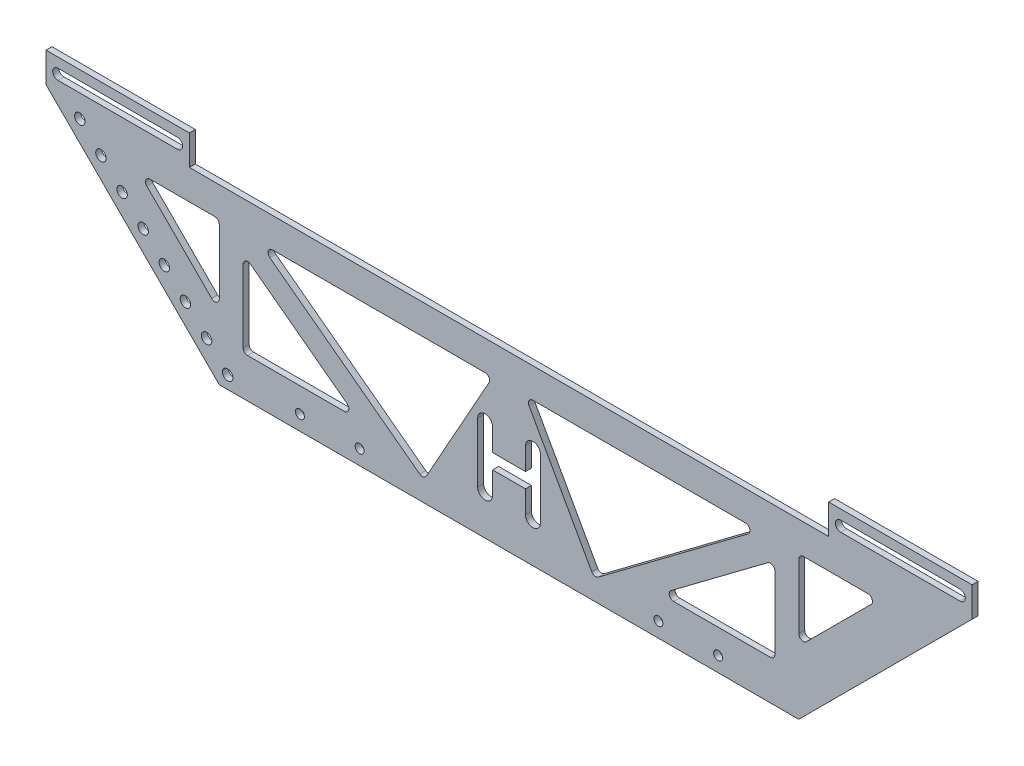
SolidWorks part; units mm, degrees
material "6061 合金"
ref_plane "前视基准面" through (0, 0, 0) normal (0, 0, 1) x (1, 0, 0)
ref_plane "上视基准面" through (0, 0, 0) normal (0, 1, 0) x (1, 0, 0)
ref_plane "右视基准面" through (0, 0, 0) normal (1, 0, 0) x (0, 0, -1)
sketch "草图1" plane through (0, 0, 0) normal (0, 0, 1) x (1, 0, 0)
  line L0 (-107, 30) -> (-107, 0)
  line L1 (-107, 0) -> (107, 0)
  line L2 (107, 0) -> (107, 30)
  line L3 (-107, 30) -> (-155, 30)
  line L5 (-97, -58) -> (97, -58)
  line L7 (155, 30) -> (107, 30)
  line L8 (0, 0) -> (0, -58) construction
  line L9 (-151, 25) -> (-111, 25) construction
  line L10 (-151, 25) -> (-151, 5) construction
  line L11 (-151, 5) -> (-111, 5) construction
  line L12 (-111, 25) -> (-111, 5) construction
  line L13 (111, 25) -> (111, 5) construction
  line L14 (151, 5) -> (111, 5) construction
  line L15 (151, 25) -> (151, 5) construction
  line L16 (151, 25) -> (111, 25) construction
  line L17 (-70, -53) -> (-50, -53) construction
  line L18 (70, -53) -> (50, -53) construction
  line L19 (-155, 30) -> (-155, 0)
  line L20 (-155, 0) -> (-97, -58)
  line L21 (97, -58) -> (155, 0)
  line L22 (155, 0) -> (155, 30)
  circle A0 centre (-151, 25) radius 1.5
  circle A1 centre (-111, 25) radius 1.5
  circle A2 centre (-111, 5) radius 1.5
  circle A3 centre (-151, 5) radius 1.5
  circle A4 centre (151, 5) radius 1.5
  circle A5 centre (111, 5) radius 1.5
  circle A6 centre (111, 25) radius 1.5
  circle A7 centre (151, 25) radius 1.5
  circle A8 centre (-70, -53) radius 1.5
  circle A9 centre (-50, -53) radius 1.5
  circle A10 centre (50, -53) radius 1.5
  circle A11 centre (70, -53) radius 1.5
  point P4 (0, 0)
  dimension "D5" = 3
  dimension "D10" = 3
  dimension "D1" = 30
  dimension "D2" = 214
  dimension "D3" = 58
  dimension "D4" = 48
  dimension "D6" = 5
  dimension "D7" = 5
  dimension "D8" = 4
  dimension "D9" = 4
  dimension "D11" = 20
  dimension "D12" = 50
  dimension "D13" = 5
  dimension "D14" = 45
extrude "凸台-拉伸1" add sketch "草图1" along normal blind 2
sketch "草图3" plane through (0, 0, 2) normal (0, 0, 1) x (1, 0, 0)
  line L0 (155, 0) -> (155, 30) construction
  line L1 (-155, 30) -> (155, 30)
  line L2 (-155, 30) -> (-155, 10)
  line L3 (-155, 10) -> (155, 10)
  line L4 (155, 30) -> (155, 10)
  circle A0 centre (151, 5) radius 1.5 construction
  dimension "D1" = 5
extrude "切除-拉伸2" cut sketch "草图3" against normal through all
sketch "草图4" plane through (0, 0, 2) normal (0, 0, 1) x (1, 0, 0)
  line L0 (-121.2261, -12.5607) -> (-99.5607, -34.2261)
  line L1 (-97, -33.1655) -> (-97, -11.5)
  line L2 (-98.5, -10) -> (-120.1655, -10)
  line L3 (107, 0) -> (-107, 0) construction
  line L4 (-155, 0) -> (-97, -58) construction
  line L5 (0, 0) -> (0, -58) construction
  line L6 (-97, -58) -> (97, -58) construction
  line L10 (-89, -19) -> (-89, -43.2868)
  line L11 (-87.5, -44.7868) -> (-55.1176, -44.7868)
  line L12 (-54.2176, -42.0868) -> (-86.6, -17.8)
  line L13 (-79.1667, -10) -> (-8, -10)
  line L14 (-6.6902, -12.231) -> (-27.6902, -49.856)
  line L15 (-29.9, -50.325) -> (-80.0667, -12.7)
  line L20 (29.9, -50.325) -> (80.0667, -12.7)
  line L21 (6.6902, -12.231) -> (27.6902, -49.856)
  line L22 (79.1667, -10) -> (8, -10)
  line L23 (54.2176, -42.0868) -> (86.6, -17.8)
  line L24 (87.5, -44.7868) -> (55.1176, -44.7868)
  line L25 (89, -19) -> (89, -43.2868)
  line L26 (98.5, -10) -> (120.1655, -10)
  line L27 (97, -33.1655) -> (97, -11.5)
  line L28 (121.2261, -12.5607) -> (99.5607, -34.2261)
  line L32 (0, 0) -> (0, -58)
  line L33 (0, -10.8561) -> (0, -58)
  line L37 (-5.5, -36.928) -> (-5.5, -44.428)
  line L41 (-5.5, -31.928) -> (5.5, -31.928)
  line L42 (-5.5, -36.928) -> (5.5, -36.928)
  line L44 (-5.5, -24.428) -> (-5.5, -31.928)
  line L45 (-10.5, -24.428) -> (-10.5, -44.428)
  line L47 (10.5, -24.428) -> (10.5, -44.428)
  line L48 (5.5, -24.428) -> (5.5, -31.928)
  line L49 (5.5, -36.928) -> (5.5, -44.428)
  arc A4 (-8, -10) -> (-6.6902, -12.231) centre (-8, -11.5) cw
  arc A5 (-27.6902, -49.856) -> (-29.9, -50.325) centre (-29, -49.125) cw
  arc A6 (-79.1667, -10) -> (-80.0667, -12.7) centre (-79.1667, -11.5) ccw
  arc A7 (-55.1176, -44.7868) -> (-54.2176, -42.0868) centre (-55.1176, -43.2868) ccw
  arc A8 (-89, -43.2868) -> (-87.5, -44.7868) centre (-87.5, -43.2868) ccw
  arc A9 (-89, -19) -> (-86.6, -17.8) centre (-87.5, -19) cw
  arc A10 (-99.5607, -34.2261) -> (-97, -33.1655) centre (-98.5, -33.1655) ccw
  arc A11 (-97, -11.5) -> (-98.5, -10) centre (-98.5, -11.5) ccw
  arc A12 (-121.2261, -12.5607) -> (-120.1655, -10) centre (-120.1655, -11.5) cw
  arc A13 (121.2261, -12.5607) -> (120.1655, -10) centre (120.1655, -11.5) ccw
  arc A14 (97, -11.5) -> (98.5, -10) centre (98.5, -11.5) cw
  arc A15 (99.5607, -34.2261) -> (97, -33.1655) centre (98.5, -33.1655) cw
  arc A16 (89, -19) -> (86.6, -17.8) centre (87.5, -19) ccw
  arc A17 (89, -43.2868) -> (87.5, -44.7868) centre (87.5, -43.2868) cw
  arc A18 (55.1176, -44.7868) -> (54.2176, -42.0868) centre (55.1176, -43.2868) cw
  arc A19 (79.1667, -10) -> (80.0667, -12.7) centre (79.1667, -11.5) cw
  arc A20 (27.6902, -49.856) -> (29.9, -50.325) centre (29, -49.125) ccw
  arc A21 (8, -10) -> (6.6902, -12.231) centre (8, -11.5) ccw
  arc A27 (-5.5, -24.428) -> (-10.5, -24.428) centre (-8, -24.428) ccw
  arc A28 (-10.5, -44.428) -> (-5.5, -44.428) centre (-8, -44.428) ccw
  arc A29 (10.5, -24.428) -> (5.5, -24.428) centre (8, -24.428) ccw
  arc A30 (5.5, -44.428) -> (10.5, -44.428) centre (8, -44.428) ccw
  point P26 (0, -34.428)
  point P32 (-8, -34.428)
  point P37 (8, -34.428)
  point P46 (-83.6667, -10)
  point P51 (-89, -44.7868)
  point P54 (-89, -16)
  point P59 (-97, -10)
  point P89 (97, -10)
  point P90 (89, -16)
  point P91 (89, -44.7868)
  point P92 (83.6667, -10)
  dimension "D7" = 1.5
  dimension "D1" = 10
  dimension "D2" = 15
  dimension "D3" = 8
  dimension "D4" = 8
  dimension "D5" = 6
  dimension "D6" = 8
  dimension "D8" = 29
extrude "切除-拉伸3" cut sketch "草图4" against normal through all and the other way through all contours L49 A30 L47 A29 L48 L41 L33 L42 | L45 A28 L37 L42 L33 L41 L44 A27 | L13 A6 L15 A5 L14 A4 | A9 L10 A8 L11 A7 L12 | A12 L0 A10 L1 A11 L2 | L22 A21 L21 A20 L20 A19 | A18 L24 A17 L25 A16 L23 | A15 L28 A13 L26 A14 L27 region at (-105.8777, -18.8777, 2) region at (-76.3188, -35.1852, 2) region at (-39.1442, -23.8182, 2) region at (39.1442, -23.8182, 2) region at (76.3188, -35.1852, 2) region at (105.8777, -18.8777, 2) region at (7.0188, -34.428, 2) region at (-7.0188, -34.428, 2)
sketch "草图5" plane through (0, 0, 2) normal (0, 0, 1) x (1, 0, 0)
  line L0 (-151, 5) -> (-111, 5) construction
  line L1 (-151, 6.75) -> (-111, 6.75)
  line L2 (-151, 3.25) -> (-111, 3.25)
  line L3 (111, 5) -> (151, 5) construction
  line L4 (111, 6.75) -> (151, 6.75)
  line L5 (111, 3.25) -> (151, 3.25)
  arc A0 (-151, 6.75) -> (-151, 3.25) centre (-151, 5) ccw
  arc A1 (-111, 3.25) -> (-111, 6.75) centre (-111, 5) ccw
  arc A2 (111, 6.75) -> (111, 3.25) centre (111, 5) ccw
  arc A3 (151, 3.25) -> (151, 6.75) centre (151, 5) ccw
  point P4 (-131, 5)
  point P13 (131, 5)
extrude "切除-拉伸4" cut sketch "草图5" against normal through all
sketch "草图7" plane through (0, 0, 2) normal (0, 0, 1) x (1, 0, 0)
  line L0 (-155, 0) -> (-151.4645, 3.5355)
  line L1 (-151.4645, 3.5355) -> (-86.2465, -61.6824)
  line L2 (-126, -29) -> (-122.4645, -25.4645)
  line L3 (-155, 0) -> (-97, -58) construction
  line L4 (-122.4645, -25.4645) -> (-129.5355, -18.3934)
  line L5 (-129.5355, -18.3934) -> (-134.2335, -13.6955)
  line L6 (-129.5355, -18.3934) -> (-136.6066, -11.3223)
  line L7 (-136.6066, -11.3223) -> (-143.6777, -4.2513)
  line L8 (-122.4645, -25.4645) -> (-115.3934, -32.5355)
  line L9 (-115.3934, -32.5355) -> (-108.3223, -39.6066)
  line L10 (-108.3223, -39.6066) -> (-101.2513, -46.6777)
  line L11 (-101.2513, -46.6777) -> (-94.1802, -53.7487)
  line L12 (0, 0) -> (0, -58)
  line L13 (-97, -58) -> (97, -58) construction
  circle A0 centre (-122.4645, -25.4645) radius 1.75
  circle A1 centre (-129.5355, -18.3934) radius 1.75
  circle A2 centre (-136.6066, -11.3223) radius 1.75
  circle A3 centre (-143.6777, -4.2513) radius 1.75
  circle A4 centre (-115.3934, -32.5355) radius 1.75
  circle A5 centre (-108.3223, -39.6066) radius 1.75
  circle A6 centre (-101.2513, -46.6777) radius 1.75
  circle A7 centre (-94.1802, -53.7487) radius 1.75
  circle A8 centre (94.1802, -53.7487) radius 1.75
  circle A9 centre (101.2513, -46.6777) radius 1.75
  circle A10 centre (108.3223, -39.6066) radius 1.75
  circle A11 centre (115.3934, -32.5355) radius 1.75
  circle A12 centre (122.4645, -25.4645) radius 1.75
  circle A13 centre (129.5355, -18.3934) radius 1.75
  circle A14 centre (136.6066, -11.3223) radius 1.75
  circle A15 centre (143.6777, -4.2513) radius 1.75
  dimension "D1" = 3.5
  dimension "D2" = 10
  dimension "D3" = 10
  dimension "D4" = 10
  dimension "D5" = 10
  dimension "D6" = 10
  dimension "D7" = 10
  dimension "D8" = 10
extrude "切除-拉伸6" cut sketch "草图7" against normal through all contours L1 A7 | L1 A7 | L1 A6 | L1 A6 | L1 A5 | L1 A5 | L1 A4 | L1 A4 | L1 A0 L4 | L2 A0 L1 | L4 A0 L2 | L1 A1 L6 | L6 A1 L1 | L1 A2 L7 | L7 A2 L1 | L1 A3 | L1 A3 region at (-143.1525, -3.7261, 2) region at (-93.655, -53.2236, 2) region at (-94.7054, -54.2739, 2) region at (-100.7261, -46.1525, 2) region at (-101.7764, -47.2029, 2) region at (-107.7971, -39.0814, 2) region at (-108.8475, -40.1318, 2) region at (-114.8682, -32.0103, 2) region at (-115.9186, -33.0607, 2) region at (-121.9393, -24.9393, 2) region at (-123.5148, -25.4645, 2) region at (-129.0103, -17.8682, 2) region at (-130.0607, -18.9186, 2) region at (-136.0814, -10.7971, 2) region at (-137.1318, -11.8475, 2) region at (-144.2029, -4.7764, 2) region at (-122.4645, -26.5148, 2)
